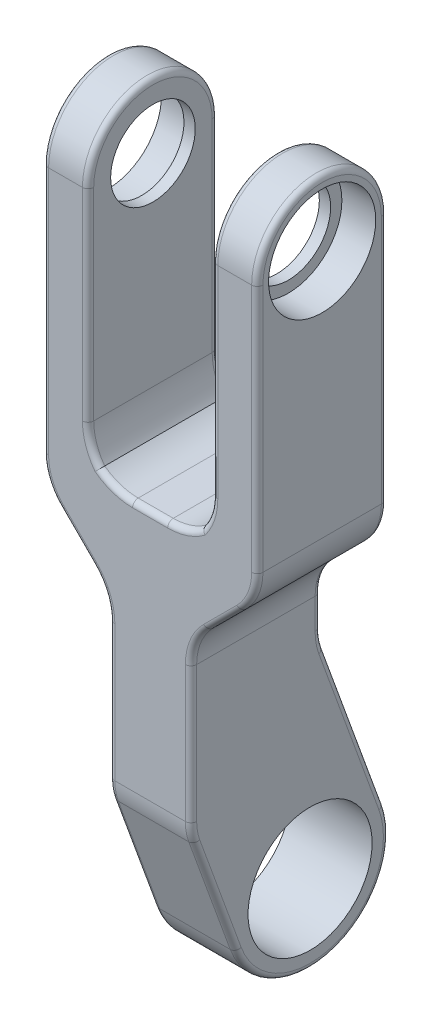
SolidWorks part; units mm, degrees
ref_plane "前视基准面" through (0, 0, 0) normal (0, 0, 1) x (1, 0, 0)
ref_plane "上视基准面" through (0, 0, 0) normal (0, 1, 0) x (1, 0, 0)
ref_plane "右视基准面" through (0, 0, 0) normal (1, 0, 0) x (0, 0, -1)
sketch "草图1" plane through (0, 0, 0) normal (0, 0, 1) x (1, 0, 0)
  line L0 (0, 0) -> (14.5, 0)
  line L1 (14.5, 0) -> (14.5, 30)
  line L2 (14.5, 30) -> (26.25, 41.75)
  line L3 (26.25, 41.75) -> (26.25, 90)
  line L4 (26.25, 90) -> (18.25, 90)
  line L5 (18.25, 90) -> (18.25, 50)
  line L6 (18.25, 50) -> (-3.75, 50)
  line L7 (-3.75, 50) -> (-3.75, 90)
  line L8 (-3.75, 90) -> (-11.75, 90)
  line L9 (-11.75, 90) -> (-11.75, 41.75)
  line L11 (0, 30) -> (0, 0)
  line L12 (0, 30) -> (-11.75, 41.75)
  line L13 (7.25, 0) -> (7.25, 35.1674) construction
  dimension "D1" = 135
  dimension "D2" = 135
  dimension "D3" = 14.5
  dimension "D4" = 8
  dimension "D5" = 8
  dimension "D6" = 22
  dimension "D7" = 90
  dimension "D8" = 30
  dimension "D9" = 40
extrude "凸台-拉伸1" add sketch "草图1" along normal blind 23
sketch "草图2" plane through (0, 0, 23) normal (0, 0, 1) x (1, 0, 0)
  line L0 (-3.75, 50) -> (0, 46.25)
  line L1 (0, 46.25) -> (14.5, 46.25)
  line L2 (14.5, 46.25) -> (18.25, 50)
  line L3 (-11.75, 41.75) -> (0, 30) construction
  line L4 (14.5, 30) -> (26.25, 41.75) construction
  line L5 (-3.75, 50) -> (18.25, 50)
extrude "切除-拉伸1" cut sketch "草图2" against normal through all
sketch "草图3" plane through (14.5, 0, 0) normal (1, 0, 0) x (0, 0, -1)
  line L0 (-23, 0) -> (0, 0)
  arc A0 (-23, 0) -> (0, 0) centre (-11.5, 0) ccw
extrude "凸台-拉伸2" [suppressed] add sketch "草图3" against normal up to surface (14.5 mm away)
sketch "草图4" [suppressed] plane through (14.5, 0, 0) normal (1, 0, 0) x (0, 0, -1)
  circle A0 centre (-11.5, 0) radius 7.5
  dimension "D1" = 15
extrude "切除-拉伸2" [suppressed] cut sketch "草图4" against normal blind 20
sketch "草图5" [suppressed] plane through (14.5, 0, 0) normal (1, 0, 0) x (0, 0, -1)
  circle A0 centre (-11.5, 0) radius 9.5
  dimension "D1" = 19
extrude "切除-拉伸3" [suppressed] cut sketch "草图5" against normal blind 6
sketch "草图6" [suppressed] plane through (0, 0, 0) normal (-1, 0, 0) x (0, 0, 1)
  circle A0 centre (11.5, 0) radius 9.5
  dimension "D1" = 19
extrude "切除-拉伸4" [suppressed] cut sketch "草图6" against normal blind 6
sketch "草图7" plane through (26.25, 0, 0) normal (1, 0, 0) x (0, 0, -1)
  line L0 (-23, 90) -> (0, 90)
  arc A0 (-23, 90) -> (0, 90) centre (-11.5, 90) cw
extrude "凸台-拉伸3" add sketch "草图7" against normal up to surface (8 mm away) up to face at (18.25, 70, 11.5)
sketch "草图8" plane through (-11.75, 0, 0) normal (-1, 0, 0) x (0, 0, 1)
  line L0 (0, 90) -> (23, 90)
  arc A0 (0, 90) -> (23, 90) centre (11.5, 90) cw
extrude "凸台-拉伸4" add sketch "草图8" against normal up to surface (8 mm away) up to face at (-3.75, 70, 11.5)
sketch "草图9" plane through (-11.75, 0, 0) normal (-1, 0, 0) x (0, 0, 1)
  circle A0 centre (11.5, 90) radius 7.5
  dimension "D1" = 15
extrude "切除-拉伸5" cut sketch "草图9" against normal blind 62
sketch "草图10" plane through (-11.75, 0, 0) normal (-1, 0, 0) x (0, 0, 1)
  circle A0 centre (11.5, 90) radius 9.5
  dimension "D1" = 19
extrude "切除-拉伸6" cut sketch "草图10" against normal blind 6
sketch "草图11" plane through (26.25, 0, 0) normal (1, 0, 0) x (0, 0, -1)
  circle A0 centre (-11.5, 90) radius 9.5
  dimension "D1" = 19
extrude "切除-拉伸7" cut sketch "草图11" against normal blind 6
sketch "草图12" plane through (14.5, 0, 0) normal (1, 0, 0) x (0, 0, -1)
  line L0 (0, 18.6745) -> (11.267, -12.2812)
  line L1 (0, 0) -> (0, 30) construction
  line L2 (-23, 0) -> (-15.0444, -21.8578)
  line L3 (-23, 0) -> (-23, 30) construction
  line L4 (11.267, -12.2812) -> (-15.0444, -21.8578)
  line L5 (-23, 0) -> (0, 18.6745)
  line L6 (0, 30) -> (0, 0) construction
  circle A1 centre (-11.5, 90) radius 9.5 construction
  point P7 (-1.8887, -17.0695)
  dimension "D1" = 200
  dimension "D2" = 28
  dimension "D3" = 107.5
extrude "凸台-拉伸5" add sketch "草图12" against normal up to surface (14.5 mm away) up to face at (0, 15, 11.5)
sketch "草图13" plane through (14.5, 0, 0) normal (1, 0, 0) x (0, 0, -1)
  line L0 (11.267, -12.2812) -> (-15.0444, -21.8578)
  arc A0 (11.267, -12.2812) -> (-15.0444, -21.8578) centre (-1.8887, -17.0695) cw
extrude "凸台-拉伸6" add sketch "草图13" against normal up to surface (14.5 mm away) up to face at (0, 7.4226, 8.2962)
sketch "草图14" plane through (14.5, 0, 0) normal (1, 0, 0) x (0, 0, -1)
  circle A0 centre (-1.8887, -17.0695) radius 11
  dimension "D1" = 22
extrude "切除-拉伸8" cut sketch "草图14" against normal up to surface (14.5 mm away) up to face at (0, 5.23, 7.4982)
fillet "圆角1" radius 10 10 edges at (7.25, 0, 23) (7.25, 18.6745, 0) (0, 30, 11.5) (-11.75, 41.75, 11.5) (14.5, 30, 11.5) (26.25, 41.75, 11.5) (0, 46.25, 11.5) (-3.75, 50, 11.5) (18.25, 50, 11.5) (14.5, 46.25, 11.5)
fillet "圆角2" radius 1 45 edges at (-3.249, 51.0164, 0) (-3.75, 72.0711, 0) (-3.75, 101.5, 11.5) (17.749, 51.0164, 0) (18.25, 72.0711, 0) (18.25, 101.5, 11.5) (14.5, 0.0268, 22.8481) (14.5, -11.7573, 18.7207) (0, -11.7573, 18.7207) (14.5, -30.2252, -2.8996) (0, 2.3682, -5.935) (14.5, 2.3682, -5.935) (14.5, 18.7013, -0.1519) (14.5, 23.1478, 0) (15.2612, 29.6847, 0) (20.375, 35.875, 0) (25.4888, 42.0653, 0) (26.25, 67.9461, 0) (26.25, 101.5, 11.5) (-11.75, 101.5, 11.5) (-11.75, 67.9461, 0) (-10.9888, 42.0653, 0) (-5.875, 35.875, 0) (-0.7612, 29.6847, 0) (0, 23.1478, 0) (0, 18.7013, -0.1519) (0, -30.2252, -2.8996) (0, 0.0268, 22.8481) (-0.7612, 29.6847, 23) (-5.875, 35.875, 23) (-10.9888, 42.0653, 23) (-11.75, 67.9461, 23) (-3.75, 72.0711, 23) (-3.249, 51.0164, 23) (1.0164, 46.751, 23) (7.25, 46.25, 23) (13.4836, 46.751, 23) (17.749, 51.0164, 23) (18.25, 72.0711, 23) (26.25, 67.9461, 23) (25.4888, 42.0653, 23) (20.375, 35.875, 23) (15.2612, 29.6847, 23) (14.5, 13.8106, 23) (0, 13.8106, 23)
